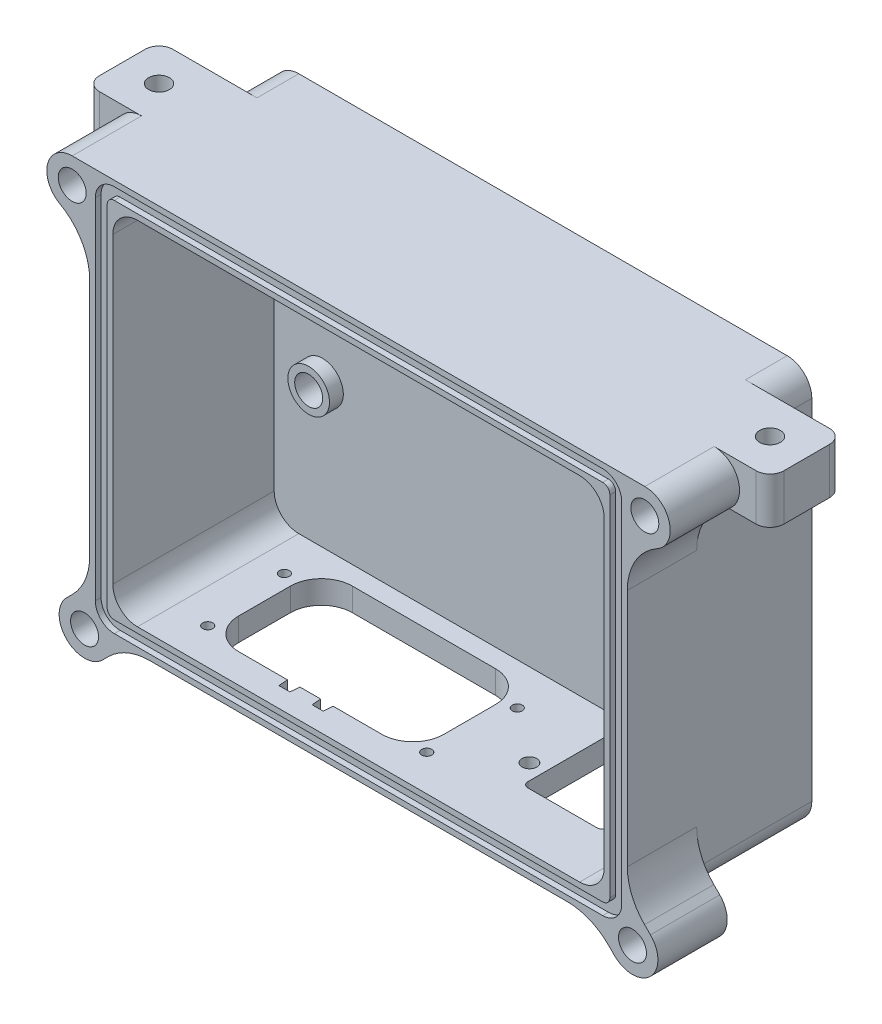
SolidWorks part; units mm, degrees
material "Custom Plastic"
ref_plane "X-Y Datum" through (0, 0, 0) normal (0, 0, 1) x (1, 0, 0)
ref_plane "X-Z Datum" through (0, 0, 0) normal (0, 1, 0) x (1, 0, 0)
ref_plane "Y-Z Datum" through (0, 0, 0) normal (1, 0, 0) x (0, 0, -1)
sketch "Sketch1" plane through (0, 0, 0) normal (0, 0, 1) x (1, 0, 0)
  line L1 (-53.1812, 38.1) -> (53.1812, 38.1)
  line L2 (-53.1812, 38.1) -> (-53.1812, -38.1)
  line L3 (-53.1812, -38.1) -> (53.1813, -38.1)
  line L4 (53.1812, 38.1) -> (53.1813, -38.1)
  line L5 (-53.1812, 38.1) -> (53.1813, -38.1) construction
  line L6 (-53.1812, -38.1) -> (53.1812, 38.1) construction
  point P0 (0, 0)
  dimension "D1" = 106.3625
  dimension "D2" = 76.2
extrude "Boss-Extrude1" add sketch "Sketch1" along normal blind 34.925
shell "Shell1" thickness 5 removed face at (0, 0, 34.925) outward yes
fillet "Fillet1" radius 5.334 8 edges at (-58.1812, -43.1, 14.9625) (58.1813, -43.1, 14.9625) (53.1812, 38.1, 17.4625) (58.1812, 43.1, 14.9625) (-58.1812, 43.1, 14.9625) (-53.1812, 38.1, 17.4625) (53.1813, -38.1, 17.4625) (-53.1812, -38.1, 17.4625)
sketch "Sketch2" plane through (0, 0, 34.925) normal (0, 0, 1) x (1, 0, 0)
  line L20 (-52.8472, -41.8827) -> (52.8473, -41.8827)
  line L21 (56.9639, -37.766) -> (56.9639, 37.766)
  line L22 (52.8472, 41.8827) -> (-52.8472, 41.8827)
  line L23 (-56.9639, 37.766) -> (-56.9639, -37.766)
  line L24 (-52.8472, -40.6) -> (52.8473, -40.6)
  line L25 (55.6812, -37.766) -> (55.6812, 37.766)
  line L26 (52.8472, 40.6) -> (-52.8472, 40.6)
  line L27 (-55.6812, 37.766) -> (-55.6812, -37.766)
  line L28 (-52.8472, -40.6) -> (52.8473, -40.6) construction
  line L29 (55.6812, -37.766) -> (55.6812, 37.766) construction
  line L30 (52.8472, 40.6) -> (-52.8472, 40.6) construction
  line L31 (-55.6812, 37.766) -> (-55.6812, -37.766) construction
  line L32 (-54.3986, 37.766) -> (-54.3986, -37.766)
  line L33 (-52.8472, -39.3173) -> (52.8473, -39.3173)
  line L34 (54.3986, -37.766) -> (54.3986, 37.766)
  line L35 (52.8472, 39.3173) -> (-52.8472, 39.3173)
  arc A16 (52.8473, -41.8827) -> (56.9639, -37.766) centre (52.8473, -37.766) ccw
  arc A17 (56.9639, 37.766) -> (52.8472, 41.8827) centre (52.8472, 37.766) ccw
  arc A18 (-52.8472, 41.8827) -> (-56.9639, 37.766) centre (-52.8472, 37.766) ccw
  arc A19 (-56.9639, -37.766) -> (-52.8472, -41.8827) centre (-52.8472, -37.766) ccw
  arc A20 (-55.6812, -37.766) -> (-52.8472, -40.6) centre (-52.8472, -37.766) ccw
  arc A21 (52.8473, -40.6) -> (55.6812, -37.766) centre (52.8473, -37.766) ccw
  arc A22 (55.6812, 37.766) -> (52.8472, 40.6) centre (52.8472, 37.766) ccw
  arc A23 (-52.8472, 40.6) -> (-55.6812, 37.766) centre (-52.8472, 37.766) ccw
  arc A24 (-55.6812, -37.766) -> (-52.8472, -40.6) centre (-52.8472, -37.766) ccw construction
  arc A25 (52.8473, -40.6) -> (55.6812, -37.766) centre (52.8473, -37.766) ccw construction
  arc A26 (55.6812, 37.766) -> (52.8472, 40.6) centre (52.8472, 37.766) ccw construction
  arc A27 (-52.8472, 40.6) -> (-55.6812, 37.766) centre (-52.8472, 37.766) ccw construction
  arc A28 (-52.8472, 39.3173) -> (-54.3986, 37.766) centre (-52.8472, 37.766) ccw
  arc A29 (-54.3986, -37.766) -> (-52.8472, -39.3173) centre (-52.8472, -37.766) ccw
  arc A30 (52.8473, -39.3173) -> (54.3986, -37.766) centre (52.8473, -37.766) ccw
  arc A31 (54.3986, 37.766) -> (52.8472, 39.3173) centre (52.8472, 37.766) ccw
  dimension "D4" = 2.5654
  dimension "D1" = 2.5
  dimension "D2" = 1.2827
  dimension "D3" = 1.2827
extrude "Cut-Extrude1" cut sketch "Sketch2" against normal blind 1.2446
sketch "Sketch4" plane through (0, 0, 34.925) normal (0, 0, 1) x (1, 0, 0)
  line L0 (56.9639, -37.766) -> (56.9639, 37.766) construction
  line L1 (52.8472, 43.1) -> (-52.8472, 43.1) construction
  line L2 (61.9639, 43.1) -> (52.8472, 43.1)
  line L3 (61.9639, 32.1) -> (58.1812, 32.1)
  line L4 (58.1813, -37.766) -> (58.1812, 37.766) construction
  line L6 (47.8473, -32.766) -> (59.2937, -44.2125)
  line L7 (55.4046, -48.1016) -> (50.4031, -43.1)
  line L8 (-52.8472, -43.1) -> (52.8473, -43.1) construction
  line L9 (63.1828, -40.3234) -> (58.1812, -35.3218)
  line L10 (-52.8472, -43.1) -> (52.8473, -43.1)
  line L11 (58.1813, -37.766) -> (58.1812, 37.766)
  circle A0 centre (61.9639, 37.6) radius 3.025
  circle A1 centre (61.9639, 37.6) radius 5.5
  arc A2 (47.8473, -38.1) -> (53.1813, -32.766) centre (47.8473, -32.766) ccw construction
  circle A3 centre (59.2937, -44.2125) radius 3.025
  circle A4 centre (59.2937, -44.2125) radius 5.5
  arc A5 (52.8473, -41.8827) -> (56.9639, -37.766) centre (52.8473, -37.766) ccw construction
  arc A6 (52.8473, -43.1) -> (58.1813, -37.766) centre (52.8473, -37.766) ccw construction
  arc A7 (58.1812, 37.766) -> (52.8472, 43.1) centre (52.8472, 37.766) ccw construction
  arc A8 (52.8473, -43.1) -> (58.1813, -37.766) centre (52.8473, -37.766) ccw
  arc A9 (58.1812, 37.766) -> (52.8472, 43.1) centre (52.8472, 37.766) ccw
  point P14 (51.619, -36.5377)
  point P23 (55.7582, -40.6769)
  dimension "D1" = 6.05
  dimension "D2" = 11
  dimension "D3" = 5
  dimension "D4" = 5
extrude "Boss-Extrude2" add sketch "Sketch4" against normal blind 15 separate body contours A9 L11 A1 A0 | A9 A1 L2 | A0 | A8 A4 L9 L11 | A8 L10 L7 A4 | A8 A4 A3 | A3 | A1 L11 L3 region at (57.3854, 42.3955, 34.925) region at (59.5123, -37.7425, 34.925) region at (65.7474, 41.3835, 34.925) region at (59.099, 32.5392, 34.925) region at (60.4186, -41.4968, 34.925) region at (64.2313, -42.1673, 34.925) region at (52.8237, -44.431, 34.925) region at (61.9639, 37.6, 34.925)
sketch "Sketch5" plane through (0, 0, 34.925) normal (0, 0, 1) x (1, 0, 0)
  line L0 (61.9639, 32.1) -> (58.1812, 32.1) construction
  line L1 (61.9639, 43.1) -> (52.8472, 43.1) construction
  line L2 (58.1813, -37.766) -> (58.1812, 37.766) construction
  line L3 (-52.8472, -43.1) -> (52.8473, -43.1) construction
  line L4 (63.1828, -40.3234) -> (58.1812, -35.3218) construction
  line L5 (55.4046, -48.1016) -> (50.4031, -43.1) construction
  line L6 (47.8473, -32.766) -> (59.2937, -44.2125) construction
  line L7 (61.9639, 32.1) -> (58.1812, 32.1)
  line L8 (61.9639, 43.1) -> (52.8472, 43.1)
  line L9 (58.1813, -37.766) -> (58.1812, 37.766)
  line L10 (-52.8472, -43.1) -> (52.8473, -43.1)
  line L11 (63.1828, -40.3234) -> (58.1812, -35.3218)
  line L12 (55.4046, -48.1016) -> (50.4031, -43.1)
  line L13 (47.8473, -32.766) -> (59.2937, -44.2125)
  arc A0 (58.1812, 37.766) -> (52.8472, 43.1) centre (52.8472, 37.766) ccw construction
  circle A1 centre (59.2937, -44.2125) radius 3.025
  circle A2 centre (59.2937, -44.2125) radius 3.025
  circle A3 centre (61.9639, 37.6) radius 5.5
  circle A4 centre (61.9639, 37.6) radius 5.5
  circle A5 centre (61.9639, 37.6) radius 3.025
  circle A6 centre (61.9639, 37.6) radius 3.025
  circle A7 centre (59.2937, -44.2125) radius 5.5
  circle A8 centre (59.2937, -44.2125) radius 5.5
  arc A9 (52.8473, -43.1) -> (58.1813, -37.766) centre (52.8473, -37.766) ccw construction
  arc A10 (58.1812, 37.766) -> (52.8472, 43.1) centre (52.8472, 37.766) ccw
  arc A11 (52.8473, -43.1) -> (58.1813, -37.766) centre (52.8473, -37.766) ccw
  dimension "D1" = 0
  dimension "D2" = 0
  dimension "D3" = 0
  dimension "D4" = 0
extrude "Cut-Extrude4" cut sketch "Sketch5" against normal blind 8 contours A6 | A2 region at (60.4186, -41.4968, 34.925) region at (61.9639, 37.6, 34.925)
mirror "Mirror3" about plane through (0, 0, 0) normal (1, 0, 0) of bodies 107 106
combine bodies "Combine3" operation type add bodies to combine 102 107 106 109 110
fillet "Fillet2" radius 12.7 6 edges at (-58.1812, 32.1, 27.425) (-50.4031, -43.1, 27.425) (-58.1812, -35.3218, 27.425) (50.4031, -43.1, 27.425) (58.1812, -35.3218, 27.425) (58.1812, 32.1, 27.425)
sketch "Sketch6" plane through (0, 0, 0) normal (0, 0, 1) x (1, 0, 0)
  line L0 (-42.7107, -5.0748) -> (-42.7107, -9.2748) construction
  line L1 (-42.7107, 20.8332) -> (-42.7107, 16.6332) construction
  line L2 (29.0253, -6.1988) -> (29.0253, -10.3988) construction
  line L3 (29.0253, 21.7412) -> (29.0253, 17.5412) construction
  circle A0 centre (-42.7107, -7.1748) radius 3.025
  circle A1 centre (-42.7107, -7.1748) radius 4.5
  circle A2 centre (-42.7107, 18.7332) radius 3.025
  circle A3 centre (-42.7107, 18.7332) radius 4.5
  circle A4 centre (29.0253, -8.2988) radius 3.025
  circle A5 centre (29.0253, -8.2988) radius 4.5
  circle A6 centre (29.0253, 19.6412) radius 3.025
  circle A7 centre (29.0253, 19.6412) radius 4.5
  spline S0 degree 3 poles (29.0253, -6.1988) (24.8253, -6.1988) (24.8253, -10.3988) (29.0253, -10.3988) (33.2253, -10.3988) (33.2253, -6.1988) (29.0253, -6.1988) (24.8253, -6.1988) (24.8253, -10.3988) knots -0.5 0 0 0 0.5 0.5 0.5 1 1 1 1.5 1.5 1.5 weights 1 0.333333 0.333333 1 0.333333 0.333333 1 0.333333 0.333333 only from (29.0253, -6.1988) to (29.0253, -6.1988) construction
  spline S1 degree 3 poles (29.0253, 21.7412) (24.8253, 21.7412) (24.8253, 17.5412) (29.0253, 17.5412) (33.2253, 17.5412) (33.2253, 21.7412) (29.0253, 21.7412) (24.8253, 21.7412) (24.8253, 17.5412) knots -0.5 0 0 0 0.5 0.5 0.5 1 1 1 1.5 1.5 1.5 weights 1 0.333333 0.333333 1 0.333333 0.333333 1 0.333333 0.333333 only from (29.0253, 21.7412) to (29.0253, 21.7412) construction
  spline S2 degree 3 poles (-42.7107, 20.8332) (-46.9107, 20.8332) (-46.9107, 16.6332) (-42.7107, 16.6332) (-38.5107, 16.6332) (-38.5107, 20.8332) (-42.7107, 20.8332) (-46.9107, 20.8332) (-46.9107, 16.6332) knots -0.5 0 0 0 0.5 0.5 0.5 1 1 1 1.5 1.5 1.5 weights 1 0.333333 0.333333 1 0.333333 0.333333 1 0.333333 0.333333 only from (-42.7107, 20.8332) to (-42.7107, 20.8332) construction
  spline S3 degree 3 poles (-42.7107, -5.0748) (-46.9107, -5.0748) (-46.9107, -9.2748) (-42.7107, -9.2748) (-38.5107, -9.2748) (-38.5107, -5.0748) (-42.7107, -5.0748) (-46.9107, -5.0748) (-46.9107, -9.2748) knots -0.5 0 0 0 0.5 0.5 0.5 1 1 1 1.5 1.5 1.5 weights 1 0.333333 0.333333 1 0.333333 0.333333 1 0.333333 0.333333 only from (-42.7107, -5.0748) to (-42.7107, -5.0748) construction
  spline S4 degree 3 poles (29.0253, -6.1988) (24.8253, -6.1988) (24.8253, -10.3988) (29.0253, -10.3988) (33.2253, -10.3988) (33.2253, -6.1988) (29.0253, -6.1988) (24.8253, -6.1988) (24.8253, -10.3988) knots -0.5 0 0 0 0.5 0.5 0.5 1 1 1 1.5 1.5 1.5 weights 1 0.333333 0.333333 1 0.333333 0.333333 1 0.333333 0.333333 only from (29.0253, -6.1988) to (29.0253, -6.1988) construction
  spline S5 degree 3 poles (29.0253, 21.7412) (24.8253, 21.7412) (24.8253, 17.5412) (29.0253, 17.5412) (33.2253, 17.5412) (33.2253, 21.7412) (29.0253, 21.7412) (24.8253, 21.7412) (24.8253, 17.5412) knots -0.5 0 0 0 0.5 0.5 0.5 1 1 1 1.5 1.5 1.5 weights 1 0.333333 0.333333 1 0.333333 0.333333 1 0.333333 0.333333 only from (29.0253, 21.7412) to (29.0253, 21.7412) construction
  spline S6 degree 3 poles (-42.7107, 20.8332) (-46.9107, 20.8332) (-46.9107, 16.6332) (-42.7107, 16.6332) (-38.5107, 16.6332) (-38.5107, 20.8332) (-42.7107, 20.8332) (-46.9107, 20.8332) (-46.9107, 16.6332) knots -0.5 0 0 0 0.5 0.5 0.5 1 1 1 1.5 1.5 1.5 weights 1 0.333333 0.333333 1 0.333333 0.333333 1 0.333333 0.333333 only from (-42.7107, 20.8332) to (-42.7107, 20.8332) construction
  spline S7 degree 3 poles (-42.7107, -5.0748) (-46.9107, -5.0748) (-46.9107, -9.2748) (-42.7107, -9.2748) (-38.5107, -9.2748) (-38.5107, -5.0748) (-42.7107, -5.0748) (-46.9107, -5.0748) (-46.9107, -9.2748) knots -0.5 0 0 0 0.5 0.5 0.5 1 1 1 1.5 1.5 1.5 weights 1 0.333333 0.333333 1 0.333333 0.333333 1 0.333333 0.333333 only from (-42.7107, -5.0748) to (-42.7107, -5.0748) construction
  dimension "D1" = 6.05
  dimension "D2" = 9
extrude "Boss-Extrude3" add sketch "Sketch6" along normal blind 3 contours A5 A4 | A4 | A7 A6 | A6 | A0 | A1 A0 | A3 A2 region at (-42.7107, -7.1748, 0) region at (-47.0835, -7.1748, 0) region at (-47.0835, 18.7332, 0) region at (29.0253, -8.2988, 0) region at (24.6525, -8.2988, 0) region at (29.0253, 19.6412, 0) region at (24.6525, 19.6412, 0)
sketch "Sketch7" plane through (0, 0, 3) normal (0, 0, 1) x (1, 0, 0)
  circle A1 centre (29.0253, -8.2988) radius 4.5
  circle A2 centre (29.0253, -8.2988) radius 4.5
  circle A3 centre (29.0253, -8.2988) radius 3.025
  circle A4 centre (29.0253, -8.2988) radius 3.025
  circle A5 centre (-42.7107, 18.7332) radius 4.5
  circle A6 centre (-42.7107, 18.7332) radius 4.5
  circle A7 centre (-42.7107, 18.7332) radius 3.025
  circle A8 centre (-42.7107, 18.7332) radius 3.025
  circle A9 centre (-42.7107, -7.1748) radius 4.5
  circle A10 centre (-42.7107, -7.1748) radius 4.5
  circle A11 centre (-42.7107, -7.1748) radius 3.025
  circle A12 centre (-42.7107, -7.1748) radius 3.025
  circle A13 centre (29.0253, 19.6412) radius 4.5
  circle A14 centre (29.0253, 19.6412) radius 4.5
  circle A15 centre (29.0253, 19.6412) radius 3.025
  circle A16 centre (29.0253, 19.6412) radius 3.025
  dimension "D1" = 0
  dimension "D2" = 0
  dimension "D3" = 0
  dimension "D4" = 0
  dimension "D5" = 0
  dimension "D6" = 0
  dimension "D7" = 0
  dimension "D8" = 0
extrude "Cut-Extrude5" cut sketch "Sketch7" against normal blind 6 contours A8 | A12 | A16 | A4 region at (29.0253, -8.2988, 3) region at (-42.7107, 18.7332, 3) region at (-42.7107, -7.1748, 3) region at (29.0253, 19.6412, 3)
sketch "Sketch8" plane through (0, 43.1, 0) normal (0, 1, 0) x (1, 0, 0)
  line L0 (0, 5) -> (0, -34.925)
  line L2 (52.8472, 5) -> (-52.8472, 5) construction
  line L3 (61.9639, -34.925) -> (-61.9639, -34.925) construction
  line L4 (-61.9639, -19.925) -> (-52.8472, -19.925) construction
  line L5 (-74.0562, -19.925) -> (74.0562, -19.925)
  line L6 (-74.0562, -19.925) -> (-74.0562, -4.05)
  line L7 (-74.0562, -4.05) -> (74.0562, -4.05)
  line L8 (74.0562, -19.925) -> (74.0562, -4.05)
  line L9 (-74.0562, -19.925) -> (74.0562, -4.05) construction
  line L10 (-74.0562, -4.05) -> (74.0562, -19.925) construction
  line L11 (-58.1812, -19.925) -> (-58.1812, 5) construction
  line L12 (-58.1812, -19.925) -> (-58.1812, -4.05)
  line L13 (-74.0562, -19.925) -> (-58.1812, -4.05)
  line L14 (52.8472, -19.925) -> (52.8472, 5) construction
  line L15 (58.1812, 5) -> (58.1812, -19.925) construction
  line L16 (52.8472, -19.925) -> (52.8472, 5)
  line L17 (58.1812, 5) -> (58.1812, -19.925)
  line L18 (58.1812, -19.925) -> (74.0562, -4.05)
  circle A0 centre (-66.1187, -11.9875) radius 2
  circle A1 centre (66.1187, -11.9875) radius 2
  point P5 (0, -11.9875)
  line M8 (61.9639, -19.925) -> (52.8472, -19.925)
  dimension "D3" = 4
  dimension "D1" = 15.875
  dimension "D2" = 15.875
extrude "Boss-Extrude4" add sketch "Sketch8" against normal blind 10 contours A0 L13 L5 L12 | A0 L13 L7 L6 | L13 A0 | L13 A0 | A1 L18 L7 L17 | L18 A1 | L18 A1 | A1 L18 L5 L8 M8 region at (-68.8719, 43.1, 9.2343) region at (-63.3656, 43.1, 14.7407) region at (-65.5185, 43.1, 12.5877) region at (-66.719, 43.1, 11.3873) region at (63.3656, 43.1, 9.2343) region at (68.8719, 43.1, 14.7407) region at (65.5185, 43.1, 11.3873) region at (66.719, 43.1, 12.5877)
sketch "Sketch9" plane through (0, 43.1, 0) normal (0, 1, 0) x (1, 0, 0)
  line L0 (-58.1812, -19.925) -> (-58.1812, -4.05) construction
  line L1 (-74.0562, -19.925) -> (-58.1812, -4.05) construction
  line L2 (0, 5) -> (0, -34.925) construction
  line L3 (-74.0562, -19.925) -> (74.0562, -19.925) construction
  line L4 (74.0562, -19.925) -> (74.0562, -4.05) construction
  line L5 (-74.0562, -4.05) -> (74.0562, -4.05) construction
  line L6 (-74.0562, -19.925) -> (-74.0562, -4.05) construction
  line L7 (-58.1812, -19.925) -> (-58.1812, -4.05)
  line L8 (-74.0562, -19.925) -> (-58.1812, -4.05)
  line L9 (0, 5) -> (0, -34.925)
  line L10 (-74.0562, -19.925) -> (74.0562, -19.925)
  line L11 (74.0562, -19.925) -> (74.0562, -4.05)
  line L12 (-74.0562, -4.05) -> (74.0562, -4.05)
  line L13 (-74.0562, -19.925) -> (-74.0562, -4.05)
  line L14 (-52.8472, 5) -> (-52.8472, -19.925) construction
  line L15 (-52.8472, 5) -> (-52.8472, -19.925)
  line L16 (52.8472, -19.925) -> (52.8472, 5) construction
  line L17 (52.8472, -19.925) -> (52.8472, 5)
  circle A0 centre (-66.1187, -11.9875) radius 2 construction
  circle A1 centre (-66.1187, -11.9875) radius 2
  line M6 (-52.8472, 5) -> (-52.8472, -19.925)
  line M7 (-52.8472, -19.925) -> (-58.1812, -19.925)
  line M8 (-58.1812, -19.925) -> (-58.1812, -4.05)
extrude "Boss-Extrude5" add sketch "Sketch9" against normal up to surface contours L12 M8 M7 M6 region at (-55.5142, 43.1, 11.9875) up to face at (-56.4895, 40.3415, 6.78)
fillet "Fillet3" radius 3 4 edges at (-74.0562, 38.1, 19.925) (-74.0562, 38.1, 4.05) (74.0562, 38.1, 19.925) (74.0562, 38.1, 4.05)
sketch "Sketch12" plane through (0, 43.1, 0) normal (0, 1, 0) x (1, 0, 0)
  line L0 (52.8472, -19.925) -> (52.8472, 5) construction
  line L1 (-52.8472, 5) -> (-52.8472, -19.925) construction
  line L2 (-58.1812, -19.925) -> (-58.1812, -4.05) construction
  line L3 (-74.0562, -19.925) -> (-58.1812, -4.05) construction
  line L4 (-74.0562, -19.925) -> (74.0562, -19.925) construction
  line L5 (74.0562, -19.925) -> (74.0562, -4.05) construction
  line L6 (-74.0562, -4.05) -> (74.0562, -4.05) construction
  line L7 (-74.0562, -19.925) -> (-74.0562, -4.05) construction
  line L8 (0, 5) -> (0, -34.925) construction
  line L9 (52.8472, -19.925) -> (52.8472, 5)
  line L10 (-52.8472, 5) -> (-52.8472, -19.925)
  line L11 (-58.1812, -19.925) -> (-58.1812, -4.05)
  line L12 (-74.0562, -19.925) -> (-58.1812, -4.05)
  line L13 (-74.0562, -19.925) -> (74.0562, -19.925)
  line L14 (74.0562, -19.925) -> (74.0562, -4.05)
  line L15 (-74.0562, -4.05) -> (74.0562, -4.05)
  line L16 (-74.0562, -19.925) -> (-74.0562, -4.05)
  line L17 (0, 5) -> (0, -34.925)
  circle A1 centre (-66.1187, -11.9875) radius 2
  circle A2 centre (-66.1187, -11.9875) radius 2
  line M12 (58.1812, -4.05) -> (58.1812, -19.925)
  line M13 (58.1812, -19.925) -> (52.8472, -19.925)
  line M14 (52.8472, -19.925) -> (52.8472, 5)
  dimension "D1" = 0
extrude "Boss-Extrude6" add sketch "Sketch12" against normal up to surface (5.334 mm away) contours L15 M14 M13 M12 region at (55.5142, 43.1, 11.9875) up to face at (56.4895, 40.3415, 6.78)
hole_wizard "M4 Clearance Hole1" positions "Sketch10" profile "Sketch11" hole size "M4" standard "ANSI Metric" end condition through all
sketch "Sketch10" plane through (0, 33.1, 0) normal (0, -1, 0) x (-1, 0, 0)
  point P0 (66.1187, -11.9875)
  point P4 (-66.1187, -11.9875)
sketch "Sketch11" plane through (-66.1187, 33.1, 11.9875) normal (1, 0, 0) x (0, 0, -1)
  line L0 (0, 0) -> (0, 10)
  line L1 (0, 10) -> (2.25, 10)
  line L2 (2.25, 10) -> (2.25, 0)
  line L5 (2.25, 0) -> (0, 0)
  line L11 (0, -6.35) -> (0, 107.95) construction
  dimension "Thru Hole Dia." = 4.5
  dimension "Thru Hole Depth" = 10
sketch "Sketch13" plane through (0, -43.1, 0) normal (0, -1, 0) x (1, 0, 0)
  line L0 (-12.2307, 28.1302) -> (-12.4056, 30.1302) construction
  line L1 (-32.2307, 28.1302) -> (-21.2307, 28.1302) construction
  line L2 (-38.4307, 10.7302) -> (-38.4307, 21.9302) construction
  line L3 (-1.2307, 4.5302) -> (-32.2307, 4.5302) construction
  line L4 (4.9693, 21.9302) -> (4.9693, 10.7302) construction
  line L5 (-12.2307, 28.1302) -> (-1.2307, 28.1302) construction
  line L6 (-21.2307, 28.1302) -> (-21.0557, 30.1302) construction
  line L7 (-21.0557, 30.1302) -> (-19.6056, 30.1302) construction
  line L8 (-19.4307, 28.1302) -> (-19.6056, 30.1302) construction
  line L9 (-19.4307, 28.1302) -> (-14.0307, 28.1302) construction
  line L10 (-14.0307, 28.1302) -> (-13.8557, 30.1302) construction
  line L11 (-13.8557, 30.1302) -> (-12.4056, 30.1302) construction
  line L12 (-12.2307, 28.1302) -> (-12.4056, 30.1302) construction
  line L13 (-13.8557, 30.1302) -> (-12.4056, 30.1302) construction
  line L14 (-14.0307, 28.1302) -> (-13.8557, 30.1302) construction
  line L15 (-19.4307, 28.1302) -> (-14.0307, 28.1302) construction
  line L16 (-19.4307, 28.1302) -> (-19.6056, 30.1302) construction
  line L17 (-21.0557, 30.1302) -> (-19.6056, 30.1302) construction
  line L18 (-21.2307, 28.1302) -> (-21.0557, 30.1302) construction
  line L19 (-12.2307, 28.1302) -> (-1.2307, 28.1302) construction
  line L36 (4.9693, 21.9302) -> (4.9693, 10.7302) construction
  line L37 (-1.2307, 4.5302) -> (-32.2307, 4.5302) construction
  line L38 (-38.4307, 10.7302) -> (-38.4307, 21.9302) construction
  line L39 (-32.2307, 28.1302) -> (-21.2307, 28.1302) construction
  line L40 (-11.7725, 28.6302) -> (-11.9475, 30.6302)
  line L41 (-14.3138, 30.6302) -> (-11.9475, 30.6302)
  line L42 (-14.4888, 28.6302) -> (-14.3138, 30.6302)
  line L43 (-18.9725, 28.6302) -> (-14.4888, 28.6302)
  line L44 (-18.9725, 28.6302) -> (-19.1475, 30.6302)
  line L45 (-21.5138, 30.6302) -> (-19.1475, 30.6302)
  line L46 (-21.6888, 28.6302) -> (-21.5138, 30.6302)
  line L47 (-32.2307, 28.6302) -> (-21.6888, 28.6302)
  line L48 (-38.9307, 10.7302) -> (-38.9307, 21.9302)
  line L49 (-1.2307, 4.0302) -> (-32.2307, 4.0302)
  line L50 (5.4693, 21.9302) -> (5.4693, 10.7302)
  line L51 (-11.7725, 28.6302) -> (-1.2307, 28.6302)
  line L52 (40.1813, 21.725) -> (40.1813, 5.275) construction
  line L53 (39.5313, 4.625) -> (24.5813, 4.625) construction
  line L54 (23.9313, 5.275) -> (23.9313, 21.725) construction
  line L55 (24.5813, 22.375) -> (39.5313, 22.375) construction
  line L56 (40.1813, 21.725) -> (40.1813, 5.275) construction
  line L57 (39.5313, 4.625) -> (24.5813, 4.625) construction
  line L58 (23.9313, 5.275) -> (23.9313, 21.725) construction
  line L59 (24.5813, 22.375) -> (39.5313, 22.375) construction
  line L60 (45.1426, 34.925) -> (-45.1426, 34.925)
  line L61 (-45.1426, 34.925) -> (-45.1426, 19.925)
  line L62 (-45.1426, 19.925) -> (-52.8473, 19.925)
  line L63 (-52.8473, 19.925) -> (-52.8472, -5)
  line L64 (-52.8472, -5) -> (52.8473, -5)
  line L65 (52.8473, -5) -> (52.8473, 19.925)
  line L66 (52.8473, 19.925) -> (45.1426, 19.925)
  line L67 (45.1426, 19.925) -> (45.1426, 34.925)
  line L74 (52.8473, 19.925) -> (45.1426, 19.925)
  line L76 (40.6813, 21.725) -> (40.6813, 5.275)
  line L77 (39.5313, 4.125) -> (24.5813, 4.125)
  line L78 (23.4313, 5.275) -> (23.4313, 21.725)
  line L79 (24.5813, 22.875) -> (39.5313, 22.875)
  arc A0 (-32.2307, 28.1302) -> (-38.4307, 21.9302) centre (-32.2307, 21.9302) ccw construction
  arc A1 (-38.4307, 10.7302) -> (-32.2307, 4.5302) centre (-32.2307, 10.7302) ccw construction
  arc A2 (-1.2307, 4.5302) -> (4.9693, 10.7302) centre (-1.2307, 10.7302) ccw construction
  arc A3 (4.9693, 21.9302) -> (-1.2307, 28.1302) centre (-1.2307, 21.9302) ccw construction
  arc A4 (4.9693, 21.9302) -> (-1.2307, 28.1302) centre (-1.2307, 21.9302) ccw construction
  arc A5 (-1.2307, 4.5302) -> (4.9693, 10.7302) centre (-1.2307, 10.7302) ccw construction
  arc A6 (-38.4307, 10.7302) -> (-32.2307, 4.5302) centre (-32.2307, 10.7302) ccw construction
  arc A7 (-32.2307, 28.1302) -> (-38.4307, 21.9302) centre (-32.2307, 21.9302) ccw construction
  arc A8 (-32.2307, 28.6302) -> (-38.9307, 21.9302) centre (-32.2307, 21.9302) ccw
  arc A9 (-38.9307, 10.7302) -> (-32.2307, 4.0302) centre (-32.2307, 10.7302) ccw
  arc A10 (-1.2307, 4.0302) -> (5.4693, 10.7302) centre (-1.2307, 10.7302) ccw
  arc A11 (5.4693, 21.9302) -> (-1.2307, 28.6302) centre (-1.2307, 21.9302) ccw
  arc A12 (40.1813, 21.725) -> (39.5313, 22.375) centre (39.5313, 21.725) ccw construction
  arc A13 (39.5313, 4.625) -> (40.1813, 5.275) centre (39.5313, 5.275) ccw construction
  arc A14 (23.9313, 5.275) -> (24.5813, 4.625) centre (24.5813, 5.275) ccw construction
  arc A15 (24.5813, 22.375) -> (23.9313, 21.725) centre (24.5813, 21.725) ccw construction
  arc A16 (40.1813, 21.725) -> (39.5313, 22.375) centre (39.5313, 21.725) ccw construction
  arc A17 (39.5313, 4.625) -> (40.1813, 5.275) centre (39.5313, 5.275) ccw construction
  arc A18 (23.9313, 5.275) -> (24.5813, 4.625) centre (24.5813, 5.275) ccw construction
  arc A19 (24.5813, 22.375) -> (23.9313, 21.725) centre (24.5813, 21.725) ccw construction
  arc A20 (39.5313, 4.125) -> (40.6813, 5.275) centre (39.5313, 5.275) ccw
  arc A21 (23.4313, 5.275) -> (24.5813, 4.125) centre (24.5813, 5.275) ccw
  arc A22 (24.5813, 22.875) -> (23.4313, 21.725) centre (24.5813, 21.725) ccw
  arc A23 (40.6813, 21.725) -> (39.5313, 22.875) centre (39.5313, 21.725) ccw
  circle A24 centre (44.0563, 9) radius 1.6 construction
  circle A25 centre (20.0563, 18) radius 1.6 construction
  arc A26 (8.0543, 27.1302) -> (5.8843, 27.1302) centre (6.9693, 27.1302) ccw construction
  arc A27 (5.8843, 27.1302) -> (8.0543, 27.1302) centre (6.9693, 27.1302) ccw construction
  arc A28 (9.5543, 9.0302) -> (7.3843, 9.0302) centre (8.4693, 9.0302) ccw construction
  arc A29 (7.3843, 9.0302) -> (9.5543, 9.0302) centre (8.4693, 9.0302) ccw construction
  arc A30 (-40.8457, 9.0302) -> (-43.0157, 9.0302) centre (-41.9307, 9.0302) ccw construction
  arc A31 (-43.0157, 9.0302) -> (-40.8457, 9.0302) centre (-41.9307, 9.0302) ccw construction
  arc A32 (-39.3457, 27.1302) -> (-41.5157, 27.1302) centre (-40.4307, 27.1302) ccw construction
  arc A33 (-41.5157, 27.1302) -> (-39.3457, 27.1302) centre (-40.4307, 27.1302) ccw construction
  circle A34 centre (44.0563, 9) radius 1.6
  circle A35 centre (20.0563, 18) radius 1.6
  arc A36 (8.0543, 27.1302) -> (5.8843, 27.1302) centre (6.9693, 27.1302) ccw
  arc A37 (5.8843, 27.1302) -> (8.0543, 27.1302) centre (6.9693, 27.1302) ccw
  arc A38 (9.5543, 9.0302) -> (7.3843, 9.0302) centre (8.4693, 9.0302) ccw
  arc A39 (7.3843, 9.0302) -> (9.5543, 9.0302) centre (8.4693, 9.0302) ccw
  arc A40 (-40.8457, 9.0302) -> (-43.0157, 9.0302) centre (-41.9307, 9.0302) ccw
  arc A41 (-43.0157, 9.0302) -> (-40.8457, 9.0302) centre (-41.9307, 9.0302) ccw
  arc A42 (-39.3457, 27.1302) -> (-41.5157, 27.1302) centre (-40.4307, 27.1302) ccw
  arc A43 (-41.5157, 27.1302) -> (-39.3457, 27.1302) centre (-40.4307, 27.1302) ccw
  point P86 (0, 0)
  dimension "D1" = 0.5
  dimension "D2" = 0
  dimension "D3" = 0.5
extrude "Cut-Extrude6" cut sketch "Sketch13" against normal blind 5 contours L50 A11 L51 L40 L41 L42 L43 L44 L45 L46 L47 A8 L48 A9 L49 A10 | L76 A23 L79 A22 L78 A21 L77 A20 | A42 A43 | A40 A41 | A38 A39 | A36 A37 | A35 | A34 region at (-16.7307, -43.1, 16.4571) region at (32.0563, -43.1, 13.5) region at (44.0563, -43.1, 9) region at (20.0563, -43.1, 18) region at (6.9693, -43.1, 27.1302) region at (8.4693, -43.1, 9.0302) region at (-41.9307, -43.1, 9.0302) region at (-40.4307, -43.1, 27.1302)
